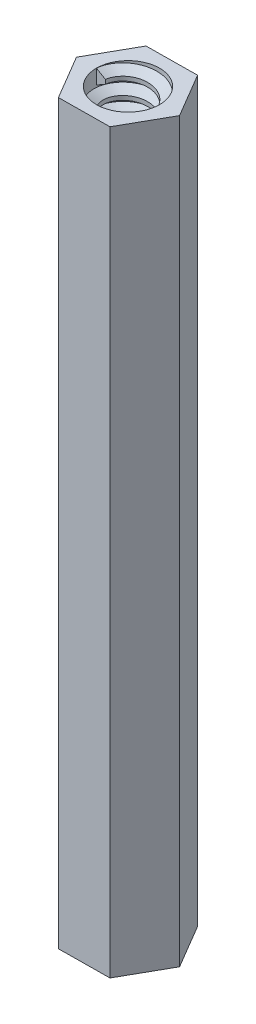
SolidWorks part; units mm, degrees
ref_plane "前视基准面" through (0, 0, 0) normal (0, 0, 1) x (1, 0, 0)
ref_plane "上视基准面" through (0, 0, 0) normal (0, 1, 0) x (1, 0, 0)
ref_plane "右视基准面" through (0, 0, 0) normal (1, 0, 0) x (0, 0, -1)
other "Configuration Table"
sketch "草图1" plane through (0, 0, 0) normal (0, 1, 0) x (1, 0, 0)
  line L1 (-1.2329, 2.088) -> (-2.4248, -0.0237)
  line L2 (-2.4248, -0.0237) -> (-1.1918, -2.1118)
  line L3 (-1.1918, -2.1118) -> (1.2329, -2.088)
  line L4 (1.2329, -2.088) -> (2.4248, 0.0237)
  line L5 (2.4248, 0.0237) -> (1.1918, 2.1118)
  line L6 (1.1918, 2.1118) -> (-1.2329, 2.088)
  circle A0 centre (0, 0) radius 2.1 construction
  dimension "D1" = 4.2
extrude "凸台-拉伸1" add sketch "草图1" along normal blind 35
sketch "草图2" plane through (0, 35, 0) normal (0, 1, 0) x (1, 0, 0)
  circle A0 centre (0, 0) radius 1.5
  dimension "D1" = 3
extrude "切除-拉伸1" cut sketch "草图2" against normal blind 5
thread "螺纹线1" pitch 0.7937 method extrude profile "螺纹线轮廓1" start angle 0, offset 0, length 5, pitch 0.7937, diameter 3
ref_plane "基准面1" through (-1.5, 35, 0) normal (0, 0, 1) x (-1, 0, 0)
sketch "螺纹线轮廓1" plane through (-1.5, 35, 0) normal (0, 0, 1) x (-1, 0, 0)
  line L0 (0, 0) -> (0, 0.7937) construction
  line L11 (0, 0) -> (0, 0.6945)
  line L12 (0, 0.6945) -> (-0.4296, 0.4465)
  line L13 (-0.4296, 0.4465) -> (-0.4296, 0.248)
  line L15 (-0.4296, 0.248) -> (0, 0)
  line L17 (-0.4296, 0.3473) -> (0, 0.3473) construction
  point P2 (0, 0)
  dimension "Pitch" = 0.7937
  dimension "Profile_Angle" = 60
  dimension "Profile_Land" = 0.1984
  dimension "Profile_Height" = 0.4296
sketch "草图7" plane through (0, 0, 0) normal (0, -1, 0) x (1, 0, 0)
  circle A0 centre (0, 0) radius 1.5
  dimension "D1" = 3
extrude "切除-拉伸2" cut sketch "草图7" against normal blind 7
thread "螺纹线2" pitch 0.7937 method extrude profile "螺纹线轮廓2" start angle 0, offset 0, length 7, pitch 0.7937, diameter 3
ref_plane "基准面2" through (1.5, 0, 0) normal (0, 0, 1) x (1, 0, 0)
sketch "螺纹线轮廓2" plane through (1.5, 0, 0) normal (0, 0, 1) x (1, 0, 0)
  line L0 (0, 0) -> (0, 0.7937) construction
  line L11 (0, 0) -> (0, 0.6945)
  line L12 (0, 0.6945) -> (-0.4296, 0.4465)
  line L13 (-0.4296, 0.4465) -> (-0.4296, 0.248)
  line L15 (-0.4296, 0.248) -> (0, 0)
  line L17 (-0.4296, 0.3473) -> (0, 0.3473) construction
  point P2 (0, 0)
  dimension "Pitch" = 0.7937
  dimension "Profile_Angle" = 60
  dimension "Profile_Land" = 0.1984
  dimension "Profile_Height" = 0.4296
